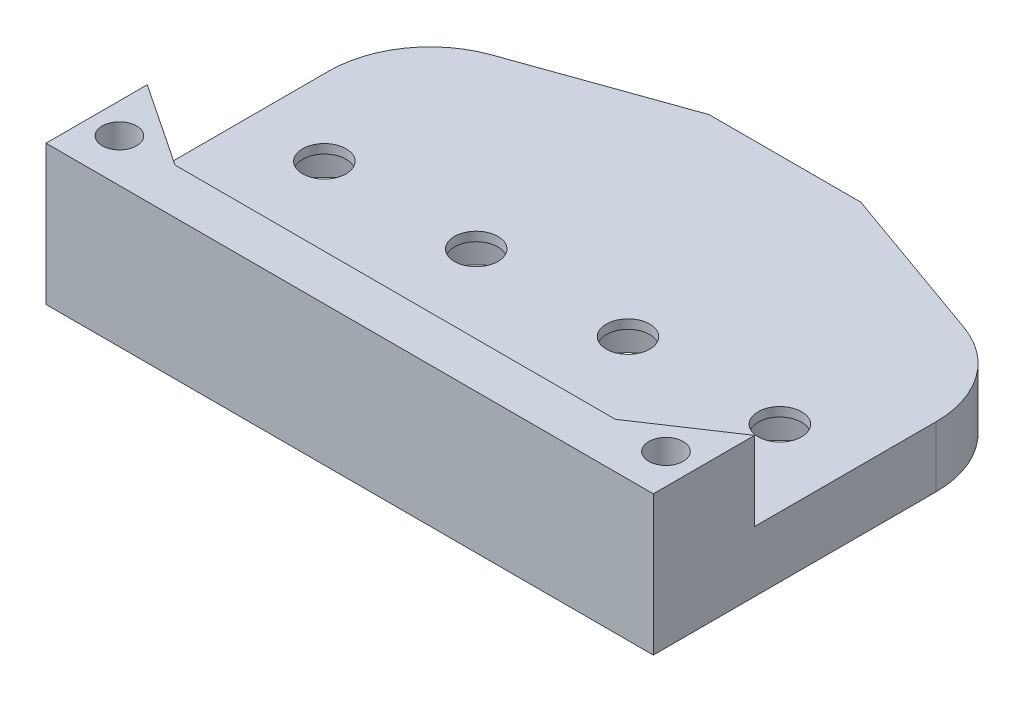
SolidWorks part; units mm, degrees
ref_plane "Front Plane" through (0, 0, 0) normal (0, 0, 1) x (1, 0, 0)
ref_plane "Top Plane" through (0, 0, 0) normal (0, 1, 0) x (1, 0, 0)
ref_plane "Right Plane" through (0, 0, 0) normal (1, 0, 0) x (0, 0, -1)
sketch "Sketch2" plane through (0, 0, 0) normal (0, 1, 0) x (1, 0, 0)
  line L0 (0, 0) -> (0, 35)
  line L1 (0, 35) -> (22.5, 43)
  line L2 (22.5, 43) -> (37.5, 43)
  line L3 (37.5, 43) -> (60, 35)
  line L4 (60, 35) -> (60, 0)
  line L5 (60, 0) -> (0, 0)
  line L6 (22.5, 20) -> (37.5, 20) construction
  line L7 (30, 43) -> (30, 0) construction
  circle A0 centre (7.5, 20) radius 2.15
  circle A1 centre (22.5, 20) radius 2.15
  circle A2 centre (37.5, 20) radius 2.15
  circle A3 centre (52.5, 20) radius 2.15
  point P17 (30, 20)
  dimension "D5" = 4.3
  dimension "D7" = 15
  dimension "D8" = 15
  dimension "D9" = 15
  dimension "D6" = 20
  dimension "D1" = 60
  dimension "D2" = 35
  dimension "D3" = 15
  dimension "D4" = 8
extrude "Boss-Extrude1" add sketch "Sketch2" along normal blind 6
sketch "Sketch3" plane through (0, 6, 0) normal (0, 1, 0) x (1, 0, 0)
  line L0 (0, 0) -> (0, 10)
  line L1 (0, 35) -> (0, 0) construction
  line L2 (0, 10) -> (15, 0)
  line L3 (0, 0) -> (60, 0) construction
  line L4 (15, 0) -> (0, 0)
  line L5 (60, 0) -> (60, 10)
  line L6 (60, 0) -> (60, 35) construction
  line L7 (60, 10) -> (45, 0)
  line L8 (45, 0) -> (60, 0)
  line L9 (51.75, 4.5) -> (8.25, 4.5)
  line M8 (0, 0) -> (60, 0)
  line M9 (60, 0) -> (60, 35)
  line M13 (0, 35) -> (0, 0)
  dimension "D1" = 15
  dimension "D2" = 10
  dimension "D3" = 4.5
extrude "Boss-Extrude2" add sketch "Sketch3" along normal blind 7.8 contours L2 M13 M8 | L7 L9 L2 M8 | L7 M9 M8 region at (5, 6, -3.3333) region at (30, 6, -2.3878) region at (55, 6, -3.3333)
sketch "Sketch4" plane through (0, 13.8, 0) normal (0, 1, 0) x (1, 0, 0)
  line L0 (0, 0) -> (60, 0) construction
  line L1 (0, 10) -> (0, 0) construction
  line L2 (60, 0) -> (60, 10) construction
  circle A0 centre (3, 4.25) radius 1.7
  circle A1 centre (57, 4.25) radius 1.7
  dimension "D1" = 3.4
  dimension "D2" = 4.25
  dimension "D3" = 3
  dimension "D4" = 3
extrude "Cut-Extrude1" cut sketch "Sketch4" against normal through all
sketch "Sketch5" plane through (0, 0, 0) normal (0, 1, 0) x (1, 0, 0)
  circle A0 centre (7.5, 20) radius 6.55
  circle A1 centre (22.5, 20) radius 6.55
  circle A2 centre (37.5, 20) radius 6.55
  circle A3 centre (52.5, 20) radius 6.55
  dimension "D1" = 13.1
extrude "Cut-Extrude2" cut sketch "Sketch5" along normal blind 5.1
fillet "Fillet1" radius 10 2 edges at (0, 3, -35) (60, 3, -35)
sketch "Sketch6" plane through (0, 0, 0) normal (0, -1, 0) x (-1, 0, 0)
  circle A0 centre (-23.6954, 36.6768) radius 2.6
  circle A1 centre (-33.6954, 36.6768) radius 2.6
  dimension "D1" = 5.2
  dimension "D2" = 10
